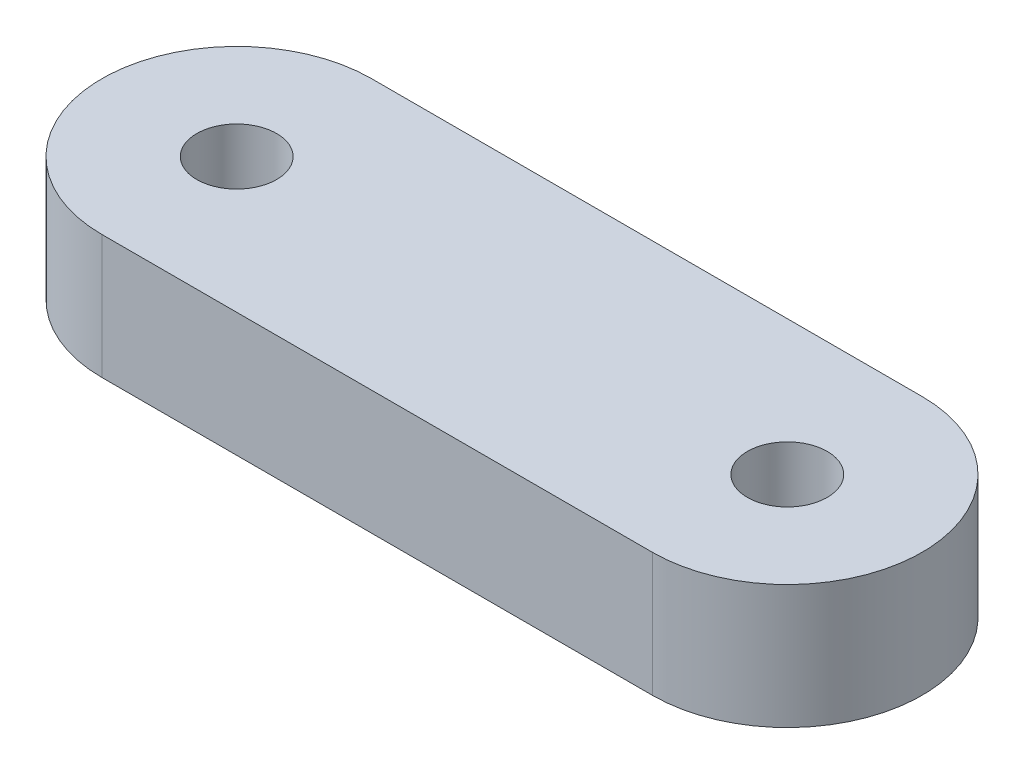
SolidWorks part; units mm, degrees
ref_plane "Front Plane" through (0, 0, 0) normal (0, 0, 1) x (1, 0, 0)
ref_plane "Top Plane" through (0, 0, 0) normal (0, 1, 0) x (1, 0, 0)
ref_plane "Right Plane" through (0, 0, 0) normal (1, 0, 0) x (0, 0, -1)
sketch "Sketch1" plane through (0, 0, 0) normal (0, 1, 0) x (1, 0, 0)
  line L0 (14.9, 0) -> (14.9, 15.5804) construction
  line L1 (-10, 4.9) -> (10, 4.9)
  line L2 (-14.9, 0) -> (-14.9, 15.5804) construction
  line L3 (-10, -4.9) -> (10, -4.9)
  line L4 (-10, 4.9) -> (-10, -4.9) construction
  line L5 (-10, 4.9) -> (10, -4.9) construction
  line L6 (-10, -4.9) -> (10, 4.9) construction
  line L7 (10, 4.9) -> (10, -4.9) construction
  line L8 (0, 4.9) -> (0, -4.9) construction
  arc A0 (-10, 4.9) -> (-10, -4.9) centre (-10, 0) ccw
  arc A1 (10, -4.9) -> (10, 4.9) centre (10, 0) ccw
  circle A2 centre (-10, 0) radius 1.45
  circle A3 centre (10, 0) radius 1.45
  point P0 (0, 0)
  dimension "D4" = 4.9
  dimension "D5" = 2.9
  dimension "D1" = 9.8
  dimension "D2" = 20
extrude "Boss-Extrude1" add sketch "Sketch1" along normal blind 4.5
equation "\"Y-ROD-SPACING\"=75"
equation "\"Y-BED-OFFSET\"=2"
equation "\"Y-BED-ROD-INSET\"=3.5"
equation "\"T-SLOT-NUT-FILLET-RADIUS\"=0.5"
equation "\"T-SLOT-SCREW-SHAFT-RADIUS\"=1.55"
equation "\"T-SLOT-SCREW-SHAFT-CUTOUT-LENGTH\"=11"
equation "\"T-SLOT-NUT-DEPTH\"=3.5"
equation "\"T-SLOT-NUT-WIDTH\"=2.85"
equation "\"T-SLOT-NUT-END-DISTANCE\"=8"
equation "\"ACRYLIC-TAB-CUTOUT-SIZE\"=\"ACRYLIC-THICKNESS\"+\"ACRYLIC-TAB-TOLERANCE\"*2"
equation "\"ACRYLIC-M3-HOLE\"=2.9"
equation "\"D5@Sketch1\"=\"ACRYLIC-M3-HOLE\""
equation "\"SMOOTHROD-CAP-SCREW-DISTANCE\"=20"
equation "\"D2@Sketch1\"=\"SMOOTHROD-CAP-SCREW-DISTANCE\""
equation "\"X-ROD-SPACING\"=45"
equation "\"Z-ROD-SPACING\"=17.5"
equation "\"ACRYLIC-THICKNESS\"=10"
equation "\"ACRYLIC-THICKNESS2\"=4.5"
equation "\"ACRYLIC-TAB-WIDTH\"=\"ACRYLIC-THICKNESS\""
equation "\"FRAME-WIDTH-INNER\"=370"
equation "\"NEMA17-HOLE-SPACING\"=31"
equation "\"NEMA17-CENTRAL-CUTOUT\"=22.5"
equation "\"Z-BRACKET-REACH\"=55"
equation "\"TOP-BRACKET-SPACING\"=40"
equation "\"SMOOTHROD-X-LENGTH\"=350"
equation "\"SMOOTHROD-Y-LENGTH\"=350"
equation "\"SMOOTHROD-Z-LENGTH\"=350"
equation "\"SMOOTHROD-TIGHTENING-HEADROOM\"=.25"
equation "\"LEADSCREW-Z-LENGTH\"=300"
equation "\"SCREW-LENGTH-FRAME\"=\"ACRYLIC-THICKNESS\" + 10"
equation "\"SCREW-HEAD-RADIUS\"=6"
equation "\"PRINTED-X-SMOOTHROD-DIAMETER\"=8.8"
equation "\"PRINTED-X-SMOOTHROD-CUTOUT\"=10"
equation "\"PRINTED-X-BASE-HEIGHT\"=10"
equation "\"PRINTED-LM8UU-CUTOUT-SIZE\"=15.5"
equation "\"PRINTED-LM8UU-CUTOUT-LENGTH\"=24.5"
equation "\"PRINTED-X-IDLER-HEIGHT\"=16"
equation "\"PSU-MOUNTING-WIDTH\"=95"
equation "\"PSU-MOUNTING-HEIGHT\"=177"
equation "\"D1@Boss-Extrude1\"=\"ACRYLIC-THICKNESS2\""
